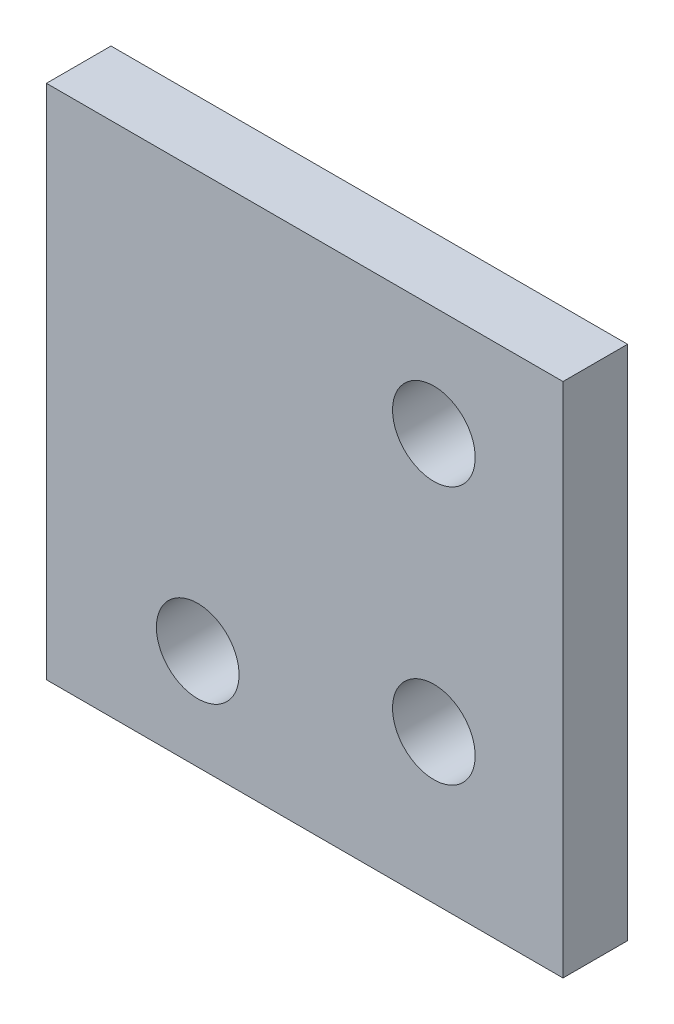
SolidWorks part; units mm, degrees
ref_plane "Front Plane" through (0, 0, 0) normal (0, 0, 1) x (1, 0, 0)
ref_plane "Top Plane" through (0, 0, 0) normal (0, 1, 0) x (1, 0, 0)
ref_plane "Right Plane" through (0, 0, 0) normal (1, 0, 0) x (0, 0, -1)
sketch "Sketch1" plane through (0, 0, 0) normal (0, 0, 1) x (1, 0, 0)
  line L1 (-12.7, -12.7) -> (12.7, -12.7)
  line L2 (-12.7, -12.7) -> (-12.7, 12.7)
  line L3 (-12.7, 12.7) -> (12.7, 12.7)
  line L4 (12.7, -12.7) -> (12.7, 12.7)
  line L5 (-12.7, -12.7) -> (12.7, 12.7) construction
  line L6 (-12.7, 12.7) -> (12.7, -12.7) construction
  point P0 (0, 0)
  dimension "D1" = 25.4
  dimension "D2" = 25.4
extrude "Boss-Extrude1" add sketch "Sketch1" along normal blind 3.175
sketch "Sketch2" plane through (0, 0, 0) normal (0, 0, -1) x (-1, 0, 0)
  circle A0 centre (5.2605, -7.7564) radius 2.032 construction
  circle A1 centre (-6.35, -5.3969) radius 2.032 construction
  circle A2 centre (-6.35, 7.3031) radius 2.032 construction
  circle A3 centre (5.2605, -7.7564) radius 2.032
  circle A4 centre (-6.35, -5.3969) radius 2.032
  circle A5 centre (-6.35, 7.3031) radius 2.032
extrude "Cut-Extrude1" cut sketch "Sketch2" against normal through all both and the other way through all
